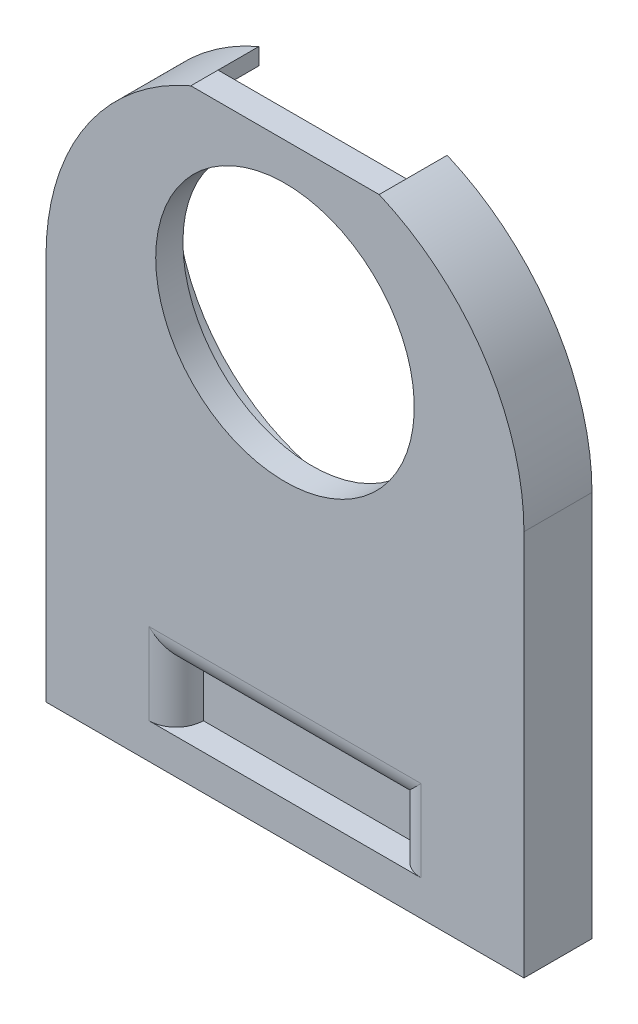
SolidWorks part; units mm, degrees
ref_plane "Front Plane" through (0, 0, 0) normal (0, 0, 1) x (1, 0, 0)
ref_plane "Top Plane" through (0, 0, 0) normal (0, 1, 0) x (1, 0, 0)
ref_plane "Right Plane" through (0, 0, 0) normal (1, 0, 0) x (0, 0, -1)
sketch "Sketch1" plane through (0, 0, 0) normal (0, 0, 1) x (1, 0, 0)
  line L0 (5.32, 14.0026) -> (5.32, 14.6195)
  line L1 (0, 0) -> (17.56, 0)
  line L2 (0, 0) -> (0, 6.55)
  line L3 (0, 6.55) -> (17.56, 6.55)
  line L4 (17.56, 0) -> (17.56, 6.55)
  line L6 (12.24, 14.0026) -> (12.24, 14.6195)
  arc A0 (5.32, 14.6195) -> (0, 6.55) centre (8.78, 6.55) ccw
  arc A1 (5.32, 14.0026) -> (12.24, 14.0026) centre (8.78, 8.5) ccw
  arc A2 (17.56, 6.55) -> (12.24, 14.6195) centre (8.78, 6.55) ccw
  dimension "D4" = 13
  dimension "D1" = 17.56
  dimension "D2" = 6.55
  dimension "D5" = 1.95
  dimension "D6" = 5.32
extrude "Boss-Extrude1" add sketch "Sketch1" along normal blind 1.5 contours A1 L3 L2 L1 L4 | A1 L0 A0 L3 | L3 A2 L6 A1 region at (1.98, 9.9073, 0) region at (8.78, 1.8126, 0) region at (15.58, 9.9073, 0)
sketch "Sketch3" plane through (0, 0, 1.5) normal (0, 0, 1) x (1, 0, 0)
  line L5 (5.32, 14.0026) -> (5.32, 14.6195)
  line L6 (0, 6.55) -> (0, 0)
  line L7 (0, 0) -> (17.56, 0)
  line L8 (17.56, 0) -> (17.56, 6.55)
  line L9 (12.24, 14.6195) -> (12.24, 14.0026)
  line L10 (5.32, 14.0026) -> (5.32, 14.6195)
  line L11 (0, 6.55) -> (0, 0)
  line L12 (0, 0) -> (17.56, 0)
  line L13 (17.56, 0) -> (17.56, 6.55)
  line L14 (12.24, 14.6195) -> (12.24, 14.0026)
  line L15 (0, 0) -> (17.56, 0)
  line L16 (17.56, 6.55) -> (17.56, 0)
  line L17 (0, 0) -> (0, 6.55)
  line L18 (5.32, 14.6195) -> (12.24, 14.6195)
  arc A3 (5.32, 14.0026) -> (12.24, 14.0026) centre (8.78, 8.5) ccw
  arc A4 (5.32, 14.6195) -> (0, 6.55) centre (8.78, 6.55) ccw
  arc A5 (17.56, 6.55) -> (12.24, 14.6195) centre (8.78, 6.55) ccw
  arc A6 (5.32, 14.0026) -> (12.24, 14.0026) centre (8.78, 8.5) ccw
  arc A7 (5.32, 14.6195) -> (0, 6.55) centre (8.78, 6.55) ccw
  arc A8 (17.56, 6.55) -> (12.24, 14.6195) centre (8.78, 6.55) ccw
  arc A9 (17.56, 6.55) -> (12.24, 14.6195) centre (8.78, 6.55) ccw
  arc A10 (0, 6.55) -> (5.32, 14.6195) centre (8.78, 6.55) cw
  arc M9 (12.24, 14.0026) -> (5.32, 14.0026) centre (8.78, 8.5) cw
  line M10 (5.32, 14.0026) -> (5.32, 14.6195)
  arc M11 (5.32, 14.6195) -> (0, 6.55) centre (8.78, 6.55) ccw
  line M12 (0, 6.55) -> (0, 0)
  line M13 (0, 0) -> (17.56, 0)
  line M14 (17.56, 0) -> (17.56, 6.55)
  arc M15 (17.56, 6.55) -> (12.24, 14.6195) centre (8.78, 6.55) ccw
  line M16 (12.24, 14.6195) -> (12.24, 14.0026)
  dimension "D1" = 0
extrude "Boss-Extrude2" add sketch "Sketch3" along normal blind 1 contours M16 M9 M10 M11 M12 M13 M14 M15 | L18 M10 M9 M16 region at (8.78, 1.7715, 1.5) region at (8.78, 8.4788, 1.5)
sketch "Sketch4" plane through (0, 0, 1.5) normal (0, 0, -1) x (-1, 0, 0)
  circle A0 centre (-8.78, 8.5) radius 4.75
  dimension "D1" = 9.5
extrude "Cut-Extrude1" cut sketch "Sketch4" against normal through all
sketch "Sketch5" plane through (0, 0, 0) normal (0, -1, 0) x (1, 0, 0)
  line L1 (0, 2.5) -> (17.56, 2.5)
  line L2 (0, 2.5) -> (0, 0)
  line L3 (0, 0) -> (17.56, 0)
  line L4 (17.56, 2.5) -> (17.56, 0)
extrude "Boss-Extrude3" add sketch "Sketch5" along normal blind 0.15
sketch "Sketch6" plane through (0, -0.15, 0) normal (0, -1, 0) x (1, 0, 0)
  line L4 (0, 2.5) -> (0, 0)
  line L5 (0, 0) -> (17.56, 0)
  line L6 (17.56, 0) -> (17.56, 2.5)
  line L7 (17.56, 2.5) -> (0, 2.5)
  line L8 (0, 2.5) -> (0, 0)
  line L9 (0, 0) -> (17.56, 0)
  line L10 (17.56, 0) -> (17.56, 2.5)
  line L11 (17.56, 2.5) -> (0, 2.5)
  dimension "D1" = 0
extrude "Boss-Extrude4" add sketch "Sketch6" along normal blind 7.5
sketch "Sketch9" plane through (0, 0, 2.5) normal (0, 0, 1) x (1, 0, 0)
  line L0 (12.78, -4.3532) -> (17.56, -4.3532) construction
  line L1 (12.78, -6.3532) -> (4.78, -6.3532)
  line L2 (12.78, -6.3532) -> (12.78, -4.3532)
  line L3 (12.78, -4.3532) -> (4.78, -4.3532)
  line L4 (4.78, -6.3532) -> (4.78, -4.3532)
  line L5 (17.56, -7.65) -> (17.56, 6.55) construction
  line L6 (4.78, -4.3532) -> (0, -4.3532) construction
  line L7 (0, 6.55) -> (0, -7.65) construction
  dimension "D1" = 2
  dimension "D2" = 8
extrude "Cut-Extrude2" cut sketch "Sketch9" against normal blind 1
fillet "Fillet1" radius 1 3 edges at (4.78, -5.3532, 2.5) (12.78, -5.3532, 2.5) (8.78, -4.3532, 2.5)
